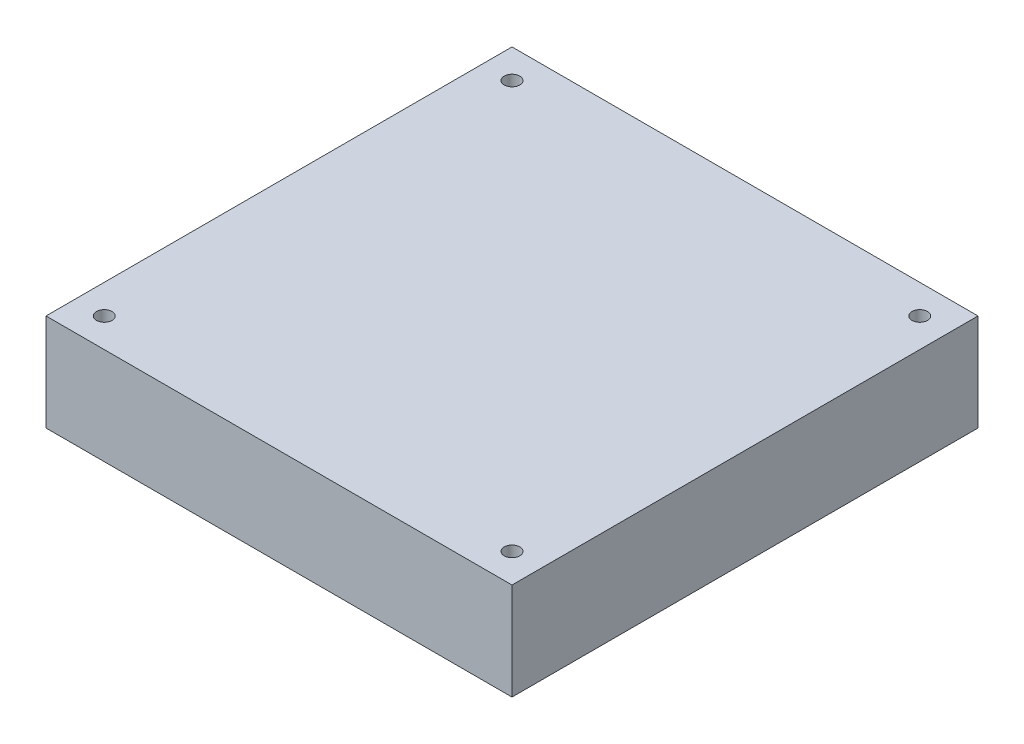
SolidWorks part; units mm, degrees
ref_plane "Front" through (0, 0, 0) normal (0, 0, 1) x (1, 0, 0)
ref_plane "Top" through (0, 0, 0) normal (0, 1, 0) x (1, 0, 0)
ref_plane "Right" through (0, 0, 0) normal (1, 0, 0) x (0, 0, -1)
sketch "Sketch1" plane through (0, 0, 0) normal (0, 1, 0) x (1, 0, 0)
  line L1 (0, 0) -> (120, 0)
  line L2 (0, 0) -> (0, -120)
  line L3 (0, -120) -> (120, -120)
  line L4 (120, 0) -> (120, -120)
  dimension "D1" = 120
  dimension "D2" = 120
extrude "Boss-Extrude1" add sketch "Sketch1" along normal blind 25
sketch "Sketch2" plane through (0, 25, 0) normal (0, 1, 0) x (1, 0, 0)
  line L0 (0, -120) -> (120, -120) construction
  line L1 (0, 0) -> (0, -120) construction
  circle A0 centre (7.5, -112.5) radius 2
  circle A1 centre (112.5, -112.5) radius 2
  circle A2 centre (112.5, -7.5) radius 2
  circle A3 centre (7.5, -7.5) radius 2
  dimension "D5" = 4
  dimension "D1" = 7.5
  dimension "D2" = 7.5
  dimension "D3" = 2
  dimension "D4" = 2
extrude "Cut-Extrude1" cut sketch "Sketch2" against normal through all
